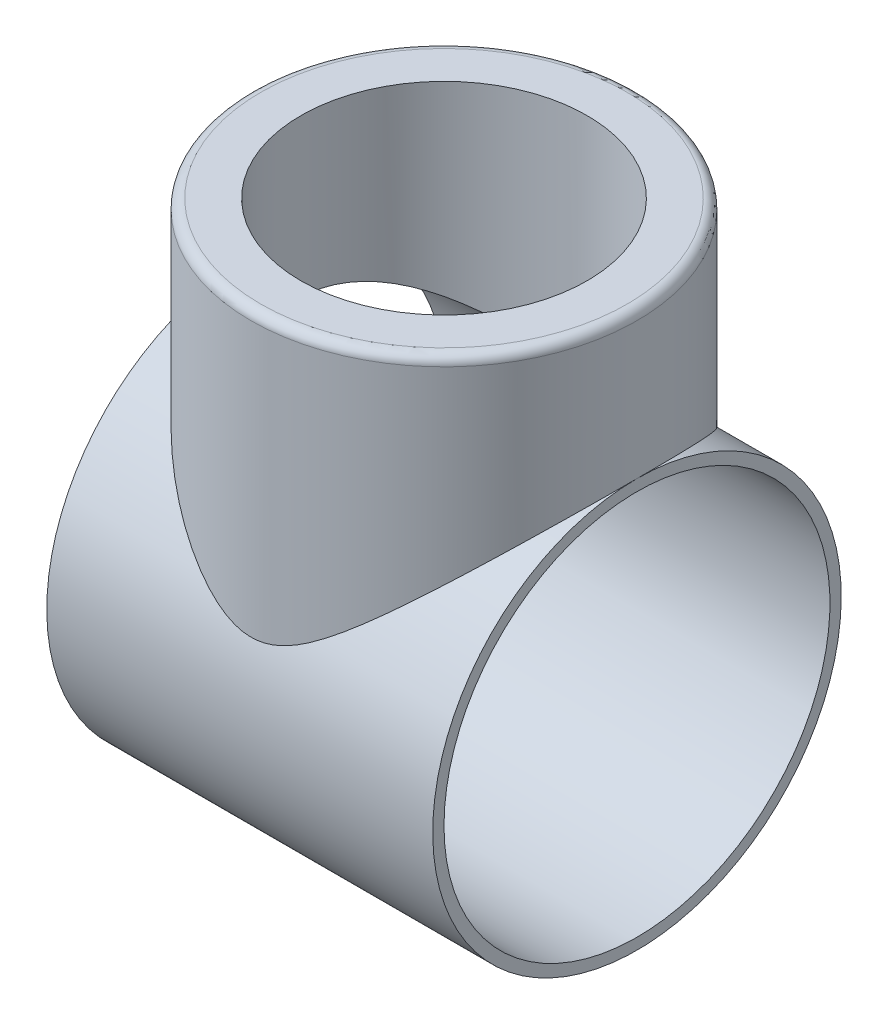
SolidWorks part; units mm, degrees
note: '?' marks a value the reader was unsure of.
ref_plane "Front Plane" through (0, 0, 0) normal (0, 0, 1) x (1, 0, 0)
ref_plane "Top Plane" through (0, 0, 0) normal (0, 1, 0) x (1, 0, 0)
ref_plane "Right Plane" through (0, 0, 0) normal (1, 0, 0) x (0, 0, -1)
ref_plane "Plane1" through (0, 0, 0) normal (0, 0, -1) x (-1, 0, 0)
sketch "Sketch1" plane through (0, 0, 0) normal (0, 0, -1) x (-1, 0, 0)
  line L0 (-60, 63.5) -> (-60, 0)
  line L1 (-60, 0) -> (60, 0)
  line L2 (60, 0) -> (60, 63.5)
  line L3 (60, 63.5) -> (-60, 63.5)
  line L4 (-60, 0) -> (60, 0) construction
revolve "Revolve1" add sketch "Sketch1" angle 360 about L4 reverse direction yes
sketch "Sketch2" plane through (0, 0, 0) normal (0, 0, 1) x (1, 0, 0)
  line L0 (0, 20.7906) -> (60, 20.7906)
  line L1 (60, 20.7906) -> (60, 109)
  line L2 (60, 109) -> (0, 109)
  line L3 (0, 109) -> (0, 20.7906)
  line L4 (0, 109) -> (0, 20.7906) construction
revolve "Revolve2" add sketch "Sketch2" angle 360 about L4 reverse direction yes
hole_wizard "Hole1" positions "Sketch4" profile "Sketch3" legacy
sketch "Sketch4" plane through (-60, 0, 0) normal (-1, 0, 0) x (0, 0, 1)
  point P0 (0, 0)
sketch "Sketch3" plane through (-60, 0, 0) normal (0, 1, 0) x (0, 0, 1)
  line L0 (0, 0) -> (0, 120)
  line L1 (0, 120) -> (60, 120)
  line L2 (60, 120) -> (60, 0)
  line L3 (60, 0) -> (0, 0)
  line L4 (0, 110) -> (0, -10) construction
  dimension "Diameter" = 120
  dimension "Depth" = 120
hole_wizard "M80 Clearance Hole1" positions "Sketch6" profile "Sketch5" hole size "M80" standard "ANSI Metric"
sketch "Sketch6" plane through (0, 109, 0) normal (0, 1, 0) x (1, 0, 0)
  point P0 (0, 0)
sketch "Sketch5" plane through (0, 109, 0) normal (1, 0, 0) x (0, 0, 1)
  line L0 (0, 0) -> (0, 49)
  line L1 (0, 49) -> (44.5, 49)
  line L2 (44.5, 49) -> (44.5, 0)
  line L5 (44.5, 0) -> (0, 0)
  line L11 (0, -6.35) -> (0, 107.95) construction
  dimension "Thru Hole Dia." = 89
  dimension "Thru Hole Depth" = 49
fillet "Fillet1" radius 3 1 edges at (0, 109, -60) tangent propagation no
ref_axis "shoulder_yaw_axis" through (0, -50.1162, 0) along (0, 1, 0)?
ref_axis "shoulder_pitch_axis"
ref_plane "Plane2" through (0, 0, 0) normal (-1, 0, 0) x (0, 0, 1)
sketch "Sketch7" plane through (0, 0, 0) normal (-1, 0, 0) x (0, 0, 1)
  circle A0 centre (0, 0) radius 27.968 construction
